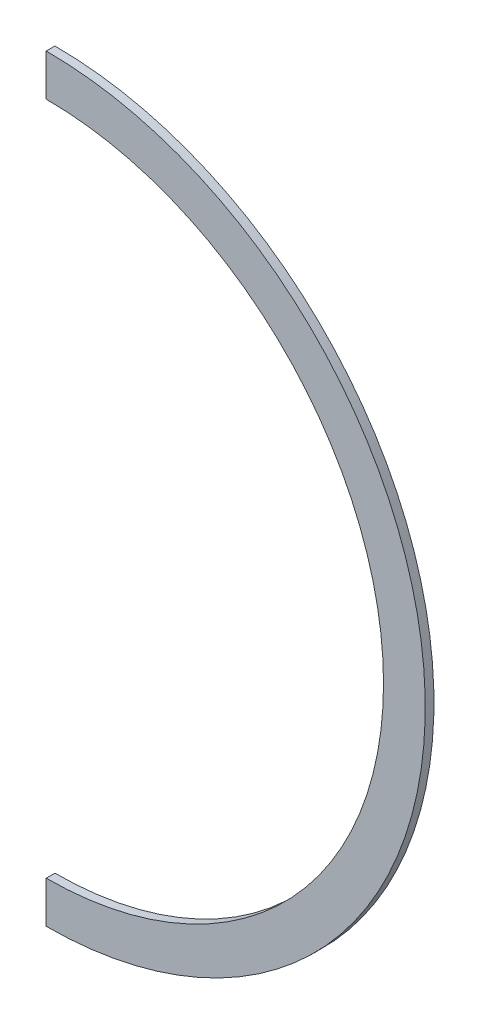
SolidWorks part; units mm, degrees
material "Balsa"
ref_plane "Front Plane" through (0, 0, 0) normal (0, 0, 1) x (1, 0, 0)
ref_plane "Top Plane" through (0, 0, 0) normal (0, 1, 0) x (1, 0, 0)
ref_plane "Right Plane" through (0, 0, 0) normal (1, 0, 0) x (0, 0, -1)
sketch "Sketch1" plane through (0, 0, 0) normal (0, 0, 1) x (1, 0, 0)
  line L0 (0, 32.094) -> (0, -346.2619) construction
  line L1 (0, 0) -> (0, 244.345) construction
  line L2 (0, 0) -> (0, 471.6969) construction
  line L3 (0, 0) -> (-283.5939, 0) construction
  line L4 (-127.2933, -32.5553) -> (-85.9841, -73.8644)
  line L5 (-85.9841, -73.8644) -> (-85.9841, -86.6438)
  line L6 (-85.9841, -73.8644) -> (-54.3993, -105.4493) construction
  arc A0 (-54.3993, -105.4493) -> (-127.2933, -32.5553) centre (0, 21.844) ccw
  arc A2 (-82.075, -89.6305) -> (-54.3993, -105.4493) centre (0, 21.844) ccw construction
  arc A3 (-127.2933, -32.5553) -> (-82.075, -89.6305) centre (0, 21.844) ccw construction
  arc A4 (-85.9841, -86.6438) -> (-54.3993, -105.4493) centre (0, 21.844) ccw
  spline S2 degree 3 poles (-1530.9406, -7642.7149) (259.0907, -1408.3953) (378.6573, 10.519) (49.9381, 150.9258) (45.7097, 152.4909) (37.1079, 155.2035) (32.7346, 156.3511) (27.1752, 157.5183) (26.0587, 157.7384) (23.8163, 158.1514) (22.6888, 158.3447) (19.306, 158.8811) (17.0511, 159.1813) (10.2867, 159.9126) (1.2693, 160.4377) (-7.745, 160.0789) (-14.5046, 159.4749) (-16.7575, 159.2176) (-20.1367, 158.7464) (-21.263, 158.5751) (-23.5156, 158.2037) (-24.6421, 158.0036) (-30.2426, 156.9366) (-34.6466, 155.8674) (-43.3063, 153.3113) (-47.562, 151.8242) (-55.9254, 148.4331) (-60.0331, 146.529) (-66.0807, 143.3516) (-68.0818, 142.2359) (-72.0044, 139.9197) (-73.9301, 138.7173) (-79.6017, 134.9792) (-86.884, 129.6473) (-93.6143, 123.6295) (-98.4521, 118.8554) (-100.0296, 117.2204) (-102.3424, 114.7015) (-103.1054, 113.8496) (-104.6077, 112.1297) (-105.3467, 111.2623) (-108.9818, 106.8875) (-111.6981, 103.2683) (-116.7574, 95.7975) (-119.1004, 91.9459) (-123.4121, 84.0098) (-125.3809, 79.9253) (-127.6006, 74.6695) (-128.0327, 73.61) (-128.8681, 71.4874) (-129.2719, 70.423) (-130.4422, 67.2205) (-131.1674, 65.0732) (-133.1812, 58.5951) (-135.4347, 49.861) (-136.834, 40.9354) (-137.5569, 34.168) (-137.7434, 31.9) (-137.9397, 28.4793) (-137.9911, 27.3374) (-138.0656, 25.0596) (-138.0887, 23.9223) (-138.135, 18.2442) (-137.9496, 13.7276) (-137.1441, 4.7454) (-136.5239, 0.2797) (-134.8456, -8.6005) (-133.7876, -13.015) (-131.2181, -21.791) (-129.7278, -26.0794) (-126.351, -34.4622) (-124.4643, -38.5569) (-120.2966, -46.5538) (-118.0156, -50.456) (-114.9122, -55.2108) (-114.2789, -56.1556) (-112.9868, -58.0327) (-112.3272, -58.9661) (-110.315, -61.7398) (-108.9333, -63.5482) (-104.6702, -68.8537) (-98.6716, -75.6089) (-92.0553, -81.7381) (-86.8592, -86.0978) (-85.0881, -87.5114) (-82.3719, -89.5716) (-81.4566, -90.2482) (-79.6058, -91.5811) (-78.6696, -92.238) (312.7351, -359.6403) (1980.7618, 1435.5712) (5240.7041, 5800.1077) knots -2.409432 -2.409432 -2.409432 -2.409432 0.03125 0.03125 0.0625 0.0625 0.09375 0.09375 0.101563 0.101563 0.109375 0.109375 0.125 0.125 0.15625 0.1875 0.1875 0.203125 0.203125 0.210937 0.210937 0.21875 0.21875 0.25 0.25 0.28125 0.28125 0.3125 0.3125 0.328125 0.328125 0.34375 0.34375 0.375 0.40625 0.40625 0.421875 0.421875 0.429687 0.429687 0.4375 0.4375 0.46875 0.46875 0.5 0.5 0.53125 0.53125 0.539062 0.539062 0.546875 0.546875 0.5625 0.5625 0.59375 0.625 0.625 0.640625 0.640625 0.648437 0.648437 0.65625 0.65625 0.6875 0.6875 0.71875 0.71875 0.75 0.75 0.78125 0.78125 0.8125 0.8125 0.84375 0.84375 0.851562 0.851562 0.859375 0.859375 0.875 0.875 0.90625 0.9375 0.9375 0.953125 0.953125 0.960937 0.960937 0.96875 0.96875 4.2021 4.2021 4.2021 4.2021 only from (66.3397, 143.1887) to (-66.0465, -100.0388)
  spline S3 degree 3 poles (66.3397, 143.1887) (62.3323, 145.3909) (58.2494, 147.3758) (49.9381, 150.9258) (45.7097, 152.4909) (37.1079, 155.2035) (32.7346, 156.3511) (27.1752, 157.5183) (26.0587, 157.7384) (23.8163, 158.1514) (22.6888, 158.3447) (19.306, 158.8811) (17.0511, 159.1813) (10.2867, 159.9126) (1.2693, 160.4377) (-7.745, 160.0789) (-14.5046, 159.4749) (-16.7575, 159.2176) (-20.1367, 158.7464) (-21.263, 158.5751) (-23.5156, 158.2037) (-24.6421, 158.0036) (-30.2426, 156.9366) (-34.6466, 155.8674) (-43.3063, 153.3113) (-47.562, 151.8242) (-55.9254, 148.4331) (-60.0331, 146.529) (-66.0807, 143.3516) (-68.0818, 142.2359) (-72.0044, 139.9197) (-73.9301, 138.7173) (-79.6017, 134.9792) (-86.884, 129.6473) (-93.6143, 123.6295) (-98.4521, 118.8554) (-100.0296, 117.2204) (-102.3424, 114.7015) (-103.1054, 113.8496) (-104.6077, 112.1297) (-105.3467, 111.2623) (-108.9818, 106.8875) (-111.6981, 103.2683) (-116.7574, 95.7975) (-119.1004, 91.9459) (-123.4121, 84.0098) (-125.3809, 79.9253) (-127.6006, 74.6695) (-128.0327, 73.61) (-128.8681, 71.4874) (-129.2719, 70.423) (-130.4422, 67.2205) (-131.1674, 65.0732) (-133.1812, 58.5951) (-135.4347, 49.861) (-136.834, 40.9354) (-137.5569, 34.168) (-137.7434, 31.9) (-137.9397, 28.4793) (-137.9911, 27.3374) (-138.0656, 25.0596) (-138.0887, 23.9223) (-138.135, 18.2442) (-137.9496, 13.7276) (-137.1441, 4.7454) (-136.5239, 0.2797) (-134.8456, -8.6005) (-133.7876, -13.015) (-131.2181, -21.791) (-129.7278, -26.0794) (-127.6847, -31.1513) (-127.3213, -32.0275) (-126.9491, -32.8995) knots 0 0 0 0 0.03125 0.03125 0.0625 0.0625 0.09375 0.09375 0.101563 0.101563 0.109375 0.109375 0.125 0.125 0.15625 0.1875 0.1875 0.203125 0.203125 0.210937 0.210937 0.21875 0.21875 0.25 0.25 0.28125 0.28125 0.3125 0.3125 0.328125 0.328125 0.34375 0.34375 0.375 0.40625 0.40625 0.421875 0.421875 0.429687 0.429687 0.4375 0.4375 0.46875 0.46875 0.5 0.5 0.53125 0.53125 0.539062 0.539062 0.546875 0.546875 0.5625 0.5625 0.59375 0.625 0.625 0.640625 0.640625 0.648437 0.648437 0.65625 0.65625 0.6875 0.6875 0.71875 0.71875 0.75 0.75 0.78125 0.78125 0.787815 0.787815 0.787815 0.787815 construction
  point P2 (0, 160.2226)
  point P3 (0, -116.9127)
  point P23 (-85.9841, -73.8644)
  dimension "D1" = 277.1353
  dimension "D2" = 276.86
  dimension "D3" = 21.844
  dimension "D5" = 45
  dimension "D6" = 113.03
  dimension "D4" = 58.42
  dimension "D7" = 45
extrude "Boss-Extrude1" add sketch "Sketch1" along normal mid plane 3.175
sketch "Sketch2" plane through (0, 0, 1.5875) normal (0, 0, 1) x (1, 0, 0)
  line L4 (-114.3729, -23.9231) -> (-70.7441, -67.5518)
  line L5 (-70.7441, -67.5518) -> (-70.7441, -79.0076)
  line L6 (-114.3729, -23.9231) -> (-70.7441, -67.5518)
  line L7 (-70.7441, -67.5518) -> (-70.7441, -79.0076)
  arc A2 (-70.7441, -79.0076) -> (-114.3729, -23.9231) centre (0, 21.844) ccw
  arc A3 (-70.7441, -79.0076) -> (-114.3729, -23.9231) centre (0, 21.844) ccw
  dimension "D1" = 15.24
extrude "Cut-Extrude1" cut sketch "Sketch2" against normal up to surface (3.175 mm away) up to face at (-27.5361, -9.1994, -1.5875)
fillet "Fillet1" radius 8.89 6 edges at (-127.2933, -32.5553, 0) (-114.3729, -23.9231, 0) (-85.9841, -73.8644, 0) (-85.9841, -86.6438, 0) (-70.7441, -67.5518, 0) (-70.7441, -79.0076, 0)
sketch "Sketch3" plane through (0, 0, 1.5875) normal (0, 0, 1) x (1, 0, 0)
  line L0 (-0.0002, 49.9919) -> (-0.0176, 733.2) construction
  line L1 (-0.0002, 49.9919) -> (-0.0176, 733.2) construction
  line L2 (-136.2041, -28.3557) -> (-0.0002, 49.9919) construction
  line L3 (136.2076, -28.3488) -> (-0.0002, 49.9919) construction
  line L4 (-136.2041, -28.3557) -> (-0.0002, 49.9919) construction
  line L5 (136.2076, -28.3488) -> (-0.0002, 49.9919) construction
  line L6 (-1.6539, 152.6441) -> (-1.654, 160.2641)
  line L7 (1.6481, 152.6442) -> (1.648, 160.2642)
  line L8 (-1.6539, 152.6441) -> (1.6481, 152.6442)
  line L9 (119.8485, -45.962) -> (106.7537, -38.3747)
  line L10 (121.4435, -43.2066) -> (108.3479, -35.6188)
  line L11 (-126.0584, -33.7901) -> (-88.588, -71.2606)
  line L12 (-85.9841, -77.5468) -> (-85.9841, -82.2574)
  line L13 (-126.0584, -33.7901) -> (-88.588, -71.2606) construction
  line L14 (-85.9841, -77.5468) -> (-85.9841, -82.2574) construction
  line L18 (121.4435, -43.2066) -> (108.3479, -35.6188)
  line L30 (-123.167, -47.8929) -> (-104.8722, -37.2914)
  line L35 (119.8485, -45.962) -> (106.7537, -38.3747)
  line L47 (108.5244, -35.721) -> (120.1169, -46.1175) construction
  line L48 (114.3206, -40.9193) -> (126.5619, -48.0121) construction
  line L49 (113.8577, -42.5592) -> (122.0137, -47.2849)
  line L50 (115.5132, -39.7021) -> (123.6691, -44.4278)
  line L51 (113.8577, -42.5592) -> (115.5132, -39.7021)
  line L52 (122.0137, -47.2849) -> (123.6691, -44.4278)
  line L58 (-124.7703, -45.1423) -> (-106.4681, -34.5364)
  line L59 (-124.7703, -45.1423) -> (-123.167, -47.8929)
  line L71 (-124.7703, -45.1423) -> (-123.167, -47.8929) construction
  line L72 (-124.7703, -45.1423) -> (-106.4681, -34.5364) construction
  line L73 (-123.167, -47.8929) -> (-104.8722, -37.2914) construction
  line L74 (-123.167, -47.8929) -> (-107.9499, -35.3951) construction
  line L75 (-115.5584, -41.644) -> (-110.9064, -38.9482) construction
  line L76 (-119.3826, -41.9518) -> (-112.6266, -38.0369)
  line L77 (-117.727, -44.8088) -> (-110.971, -40.8938)
  line L78 (-119.3826, -41.9518) -> (-117.727, -44.8088)
  line L79 (-112.6266, -38.0369) -> (-110.971, -40.8938)
  arc A0 (-54.3993, -105.4493) -> (-127.2933, -32.5553) centre (0, 21.844) ccw construction
  arc A2 (-1.654, 160.2641) -> (-130.2816, -24.9489) centre (0, 21.844) ccw construction
  arc A3 (-130.2816, -24.9489) -> (-127.2933, -32.5553) centre (0, 21.844) ccw construction
  arc A4 (-1.654, 160.2641) -> (-130.2816, -24.9489) centre (0, 21.844) ccw construction
  arc A5 (-130.2816, -24.9489) -> (-127.9919, -30.8906) centre (0, 21.844) ccw construction
  arc A6 (-82.3849, -89.4016) -> (-127.9919, -30.8906) centre (0, 21.844) ccw
  arc A7 (-127.9919, -30.8906) -> (-126.0584, -33.7901) centre (-119.7722, -27.504) ccw
  arc A8 (-85.9841, -77.5468) -> (-88.588, -71.2606) centre (-94.8741, -77.5468) ccw
  arc A9 (-85.9841, -82.2574) -> (-82.3849, -89.4016) centre (-77.0941, -82.2574) ccw
  arc A11 (-127.9919, -30.8906) -> (-126.0584, -33.7901) centre (-119.7722, -27.504) ccw construction
  arc A12 (-85.9841, -77.5468) -> (-88.588, -71.2606) centre (-94.8741, -77.5468) ccw construction
  arc A13 (-85.9841, -82.2574) -> (-82.3849, -89.4016) centre (-77.0941, -82.2574) ccw construction
  arc A14 (130.2841, -24.9419) -> (1.648, 160.2642) centre (0, 21.844) ccw construction
  arc A15 (1.648, 160.2642) -> (-1.654, 160.2641) centre (0, 21.844) ccw
  arc A16 (130.2841, -24.9419) -> (1.648, 160.2642) centre (0, 21.844) ccw construction
  arc A17 (1.648, 160.2642) -> (-1.654, 160.2641) centre (0, 21.844) ccw
  spline S0 degree 3 poles (106.7537, -38.3747) (107.2851, -37.456) (107.8165, -36.5374) (108.3479, -35.6188) knots 0 0 0 0 1 1 1 1 weights 1 1 1 1
  spline S1 degree 3 poles (119.8485, -45.962) (120.3802, -45.0435) (120.9118, -44.1251) (121.4435, -43.2066) knots 0 0 0 0 1 1 1 1 weights 1 1 1 1
  spline S2 degree 3 poles (-885.9096, -1769.7959) (-211.5315, -623.0099) (457.4335, 532.6653) (1115.294, 1687.3986) knots -628.025755 -628.025755 -628.025755 -628.025755 629.32196 629.32196 629.32196 629.32196 weights 1.00213 0.999289 0.99929 1.002132 only from (119.8485, -45.962) to (121.4435, -43.2066)
  spline S3 degree 3 poles (-1102.9631, 1696.4301) (-441.8977, 540.8873) (227.2766, -614.259) (901.0121, -1762.8827) knots -628.210575 -628.210575 -628.210575 -628.210575 629.142222 629.142222 629.142222 629.142222 weights 1.001328 0.999558 0.999557 1.001327 only from (-106.4681, -34.5364) to (-104.8722, -37.2914)
  spline S4 degree 3 poles (-106.4681, -34.5364) (-105.9361, -35.4547) (-105.4042, -36.373) (-104.8722, -37.2914) knots 0 0 0 0 1 1 1 1 weights 1 1 1 1 construction
  spline S6 degree 3 poles (-898.3985, -1763.0369) (-224.3104, -615.0446) (444.2624, 540.7506) (1102.1878, 1695.4772) knots -627.922228 -627.922228 -627.922228 -627.922228 629.425892 629.425892 629.425892 629.425892 weights 1.001921 0.999359 0.99936 1.001924 only from (106.7537, -38.3747) to (108.3479, -35.6188)
  point P49 (-116.0256, -43.8229)
  point P50 (120.451, -46.3794)
  arc M19 (-82.3849, -89.4016) -> (-127.9919, -30.8906) centre (0, 21.844) ccw
  line M21 (-126.0584, -33.7901) -> (-88.588, -71.2606)
  dimension "D1" = 3.302
  dimension "D2" = 7.62
  dimension "D4" = 3.302
  dimension "D5" = 7.62
  dimension "D6" = 3.302
  dimension "D7" = 5.842
  dimension "D3" = 0
extrude "Cut-Extrude2" [suppressed] cut sketch "Sketch3" against normal through all contours L79 L76 L77 M21 | L6 L8 L7 M19 | L51 L49 L50 M19
sketch "Sketch4" plane through (0, 0, 0) normal (1, 0, 0) x (0, 0, -1)
  line L1 (-96.2805, 232.7957) -> (122.2438, 232.7957)
  line L2 (-96.2805, 232.7957) -> (-96.2805, -207.8589)
  line L3 (-96.2805, -207.8589) -> (122.2438, -207.8589)
  line L4 (122.2438, 232.7957) -> (122.2438, -207.8589)
extrude "Cut-Extrude3" cut sketch "Sketch4" against normal through all
equation "\"a\"= 0.06"
equation "\"slotwidth\"=0.13"
equation "\"slotheight\"=0.3"
